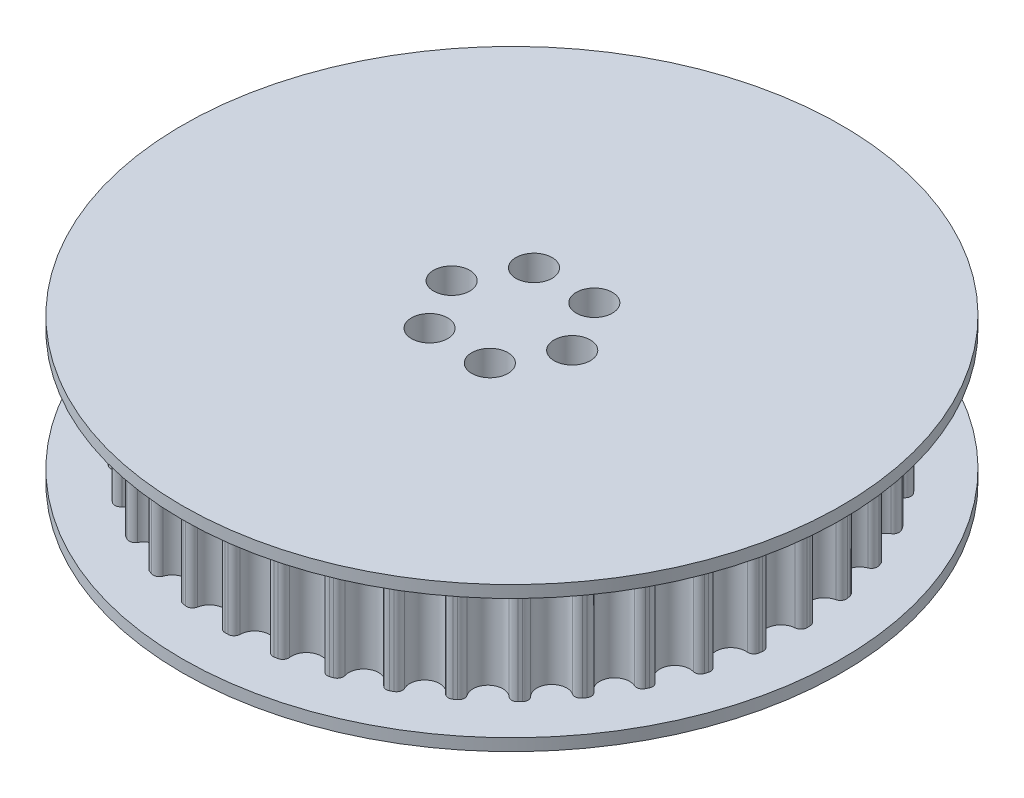
SolidWorks part; units mm, degrees
material "PETG"
ref_plane "Front Plane" through (0, 0, 0) normal (0, 0, 1) x (1, 0, 0)
ref_plane "Top Plane" through (0, 0, 0) normal (0, 1, 0) x (1, 0, 0)
ref_plane "Right Plane" through (0, 0, 0) normal (1, 0, 0) x (0, 0, -1)
sketch "Sketch5" plane through (0, 0, 0) normal (0, 1, 0) x (1, 0, 0)
  line L0 (0, 9.7022) -> (0, 50009.7022) construction
  line L1 (0, 0) -> (0, 46.5575) construction
  line L3 (0, 0) -> (-3.9957, 49.4953) construction
  line L5 (0, 0) -> (3.9957, 49.4953) construction
  circle A0 centre (0, 0) radius 49.6563 construction
  circle A2 centre (0, 0) radius 47.3449 construction
  arc A3 (-2.4772, 46.3129) -> (2.4772, 46.3129) centre (0, 46.5575) ccw
  arc A43 (3.8097, 47.1914) -> (3.5472, 47.2119) centre (0, 0) ccw
  arc A45 (-3.5472, 47.2119) -> (-3.8097, 47.1914) centre (0, 0) ccw
  arc A46 (-2.4772, 46.3129) -> (-3.5472, 47.2119) centre (-3.4723, 46.2147) ccw
  arc A47 (3.5472, 47.2119) -> (2.4772, 46.3129) centre (3.4723, 46.2147) ccw
  arc A48 (4.984, 46.1106) -> (9.8742, 45.3158) centre (7.4684, 45.9546) ccw
  arc A49 (4.984, 46.1106) -> (4.072, 47.1695) centre (3.986, 46.1732) ccw
  arc A50 (4.072, 47.1695) -> (3.8097, 47.1914) centre (0, 0) ccw
  arc A51 (11.0746, 46.0315) -> (9.8742, 45.3158) centre (10.8407, 45.0592) ccw
  arc A52 (11.3304, 45.9692) -> (11.0746, 46.0315) centre (0, 0) ccw
  arc A53 (12.3162, 44.714) -> (17.0155, 43.1451) centre (14.7433, 44.1615) ccw
  arc A54 (12.3162, 44.714) -> (11.5858, 45.9055) centre (11.3411, 44.9359) ccw
  arc A55 (11.5858, 45.9055) -> (11.3304, 45.9692) centre (0, 0) ccw
  arc A56 (18.3152, 43.6589) -> (17.0155, 43.1451) centre (17.9283, 42.7367) ccw
  arc A57 (18.5576, 43.5564) -> (18.3152, 43.6589) centre (0, 0) ccw
  arc A58 (19.3293, 42.1593) -> (23.7161, 39.8569) centre (21.6364, 41.2247) ccw
  arc A59 (19.3293, 42.1593) -> (18.7995, 43.4525) centre (18.4025, 42.5347) ccw
  arc A60 (18.7995, 43.4525) -> (18.5576, 43.5564) centre (0, 0) ccw
  arc A61 (25.0814, 40.1556) -> (23.7161, 39.8569) centre (24.5516, 39.3074) ccw
  arc A62 (25.3043, 40.0155) -> (25.0814, 40.1556) centre (0, 0) ccw
  arc A63 (25.8418, 38.5127) -> (29.8025, 35.5364) centre (27.9691, 37.2201) ccw
  arc A64 (25.8418, 38.5127) -> (25.5264, 39.8742) centre (24.9872, 39.032) ccw
  arc A65 (25.5264, 39.8742) -> (25.3043, 40.0155) centre (0, 0) ccw
  arc A66 (31.198, 35.6122) -> (29.8025, 35.5364) centre (30.539, 34.86) ccw
  arc A67 (31.3955, 35.4382) -> (31.198, 35.6122) centre (0, 0) ccw
  arc A68 (31.685, 33.8686) -> (35.117, 30.2956) centre (33.5774, 32.2515) ccw
  arc A69 (31.685, 33.8686) -> (31.5921, 35.2631) centre (30.9248, 34.5183) ccw
  arc A70 (31.5921, 35.2631) -> (31.3955, 35.4382) centre (0, 0) ccw
  arc A71 (36.5066, 30.1465) -> (35.117, 30.2956) centre (35.7355, 29.5098) ccw
  arc A72 (36.6736, 29.9431) -> (36.5066, 30.1465) centre (0, 0) ccw
  arc A73 (36.7076, 28.3474) -> (39.522, 24.2701) centre (38.3161, 26.4477) ccw
  arc A74 (36.7076, 28.3474) -> (36.8395, 29.7387) centre (36.0614, 29.1106) ccw
  arc A75 (36.8395, 29.7387) -> (36.6736, 29.9431) centre (0, 0) ccw
  arc A76 (40.8697, 23.9001) -> (39.522, 24.2701) centre (40.0064, 23.3953) ccw
  arc A77 (41.0019, 23.6725) -> (40.8697, 23.9001) centre (0, 0) ccw
  arc A78 (40.7795, 22.092) -> (42.9034, 17.616) centre (42.0624, 19.9589) ccw
  arc A79 (40.7795, 22.092) -> (41.1329, 23.4441) centre (40.2641, 22.949) ccw
  arc A80 (41.1329, 23.4441) -> (41.0019, 23.6725) centre (0, 0) ccw
  arc A81 (44.1743, 17.0346) -> (42.9034, 17.616) centre (43.2412, 16.6748) ccw
  arc A82 (44.2683, 16.7887) -> (44.1743, 17.0346) centre (0, 0) ccw
  arc A83 (43.7952, 15.2644) -> (45.1736, 10.5057) centre (44.7194, 12.9531) ccw
  arc A84 (43.7952, 15.2644) -> (44.361, 16.5424) centre (43.424, 16.193) ccw
  arc A85 (44.361, 16.5424) -> (44.2683, 16.7887) centre (0, 0) ccw
  arc A86 (46.3348, 9.728) -> (45.1736, 10.5057) centre (45.3561, 9.5225) ccw
  arc A87 (46.3881, 9.4702) -> (46.3348, 9.728) centre (0, 0) ccw
  arc A88 (45.6767, 8.0415) -> (46.2739, 3.1233) centre (46.2181, 5.6119) ccw
  arc A89 (45.6767, 8.0415) -> (46.4401, 9.2121) centre (45.4592, 9.0176) ccw
  arc A90 (46.4401, 9.2121) -> (46.3881, 9.4702) centre (0, 0) ccw
  arc A91 (47.2952, 2.1694) -> (46.2739, 3.1233) centre (46.2963, 2.1236) ccw
  arc A92 (47.3065, 1.9064) -> (47.2952, 2.1694) centre (0, 0) ccw
  arc A93 (46.3751, 0.6103) -> (46.1756, -4.34) centre (46.5198, -1.8747) ccw
  arc A94 (46.3751, 0.6103) -> (47.3164, 1.6433) centre (46.317, 1.6086) ccw
  arc A95 (47.3164, 1.6433) -> (47.3065, 1.9064) centre (0, 0) ccw
  arc A96 (47.0307, -5.4454) -> (46.1756, -4.34) centre (46.0374, -5.3304) ccw
  arc A97 (46.9997, -5.7068) -> (47.0307, -5.4454) centre (0, 0) ccw
  arc A98 (45.8725, -6.8367) -> (44.8815, -11.6909) centre (45.6166, -9.3127) ccw
  arc A99 (45.8725, -6.8367) -> (46.9673, -5.968) centre (45.9753, -5.842) ccw
  arc A100 (46.9673, -5.968) -> (46.9997, -5.7068) centre (0, 0) ccw
  arc A101 (45.5482, -12.9191) -> (44.8815, -11.6909) centre (44.5862, -12.6463) ccw
  arc A102 (45.4757, -13.1722) -> (45.5482, -12.9191) centre (0, 0) ccw
  arc A103 (44.1818, -14.1066) -> (42.4249, -18.739) centre (43.5321, -16.5095) ccw
  arc A104 (44.1818, -14.1066) -> (45.4017, -13.4248) centre (44.4428, -13.1413) ccw
  arc A105 (45.4017, -13.4248) -> (45.4757, -13.1722) centre (0, 0) ccw
  arc A106 (42.886, -20.0583) -> (42.4249, -18.739) centre (41.9802, -19.6346) ccw
  arc A107 (42.7738, -20.2964) -> (42.886, -20.0583) centre (0, 0) ccw
  arc A108 (41.3468, -21.0112) -> (38.8696, -25.3017) centre (40.32, -23.2788) ccw
  arc A109 (41.3468, -21.0112) -> (42.6603, -20.5339) centre (41.7592, -20.1002) ccw
  arc A110 (42.6603, -20.5339) -> (42.7738, -20.2964) centre (0, 0) ccw
  arc A111 (39.1131, -26.6779) -> (38.8696, -25.3017) centre (38.2869, -26.1145) ccw
  arc A112 (38.9641, -26.895) -> (39.1131, -26.6779) centre (0, 0) ccw
  arc A113 (37.4409, -27.3716) -> (34.3076, -31.2092) centre (36.0637, -29.4451) ccw
  arc A114 (37.4409, -27.3716) -> (38.814, -27.1112) centre (37.9942, -26.5386) ccw
  arc A115 (38.814, -27.1112) -> (38.9641, -26.895) centre (0, 0) ccw
  arc A116 (34.3271, -32.6066) -> (34.3076, -31.2092) centre (33.6021, -31.9179) ccw
  arc A117 (34.1453, -32.797) -> (34.3271, -32.6066) centre (0, 0) ccw
  arc A118 (32.5653, -33.0231) -> (28.857, -36.3084) centre (30.8734, -34.8488) ccw
  arc A119 (32.5653, -33.0231) -> (33.9624, -32.9863) centre (33.2451, -32.2896) ccw
  arc A120 (33.9624, -32.9863) -> (34.1453, -32.797) centre (0, 0) ccw
  arc A121 (28.6521, -37.6908) -> (28.857, -36.3084) centre (28.0469, -36.8948) ccw
  arc A122 (28.4421, -37.8496) -> (28.6521, -37.6908) centre (0, 0) ccw
  arc A123 (26.8464, -37.8193) -> (22.659, -40.4672) centre (24.8834, -39.35) ccw
  arc A124 (26.8464, -37.8193) -> (28.2312, -38.0071) centre (27.6349, -37.2044) ccw
  arc A125 (28.2312, -38.0071) -> (28.4421, -37.8496) centre (0, 0) ccw
  arc A126 (22.235, -41.7989) -> (22.659, -40.4672) centre (21.7654, -40.916) ccw
  arc A127 (22.0023, -41.9219) -> (22.235, -41.7989) centre (0, 0) ccw
  arc A128 (20.4321, -41.636) -> (15.8742, -43.5779) centre (18.249, -42.832) ccw
  arc A129 (20.4321, -41.636) -> (21.7689, -42.0436) centre (21.3091, -41.1555) ccw
  arc A130 (21.7689, -42.0436) -> (22.0023, -41.9219) centre (0, 0) ccw
  arc A131 (15.2421, -44.8243) -> (15.8742, -43.5779) centre (14.9202, -43.8776) ccw
  arc A132 (14.9926, -44.9084) -> (15.2421, -44.8243) centre (0, 0) ccw
  arc A133 (13.4886, -44.3744) -> (8.6782, -45.56) centre (11.1419, -45.2047) ccw
  arc A134 (13.4886, -44.3744) -> (14.7427, -44.9911) centre (14.4313, -44.0408) ccw
  arc A135 (14.7427, -44.9911) -> (14.9926, -44.9084) centre (0, 0) ccw
  arc A136 (7.8544, -46.6889) -> (8.6782, -45.56) centre (7.6885, -45.7027) ccw
  arc A137 (7.5947, -46.7318) -> (7.8544, -46.6889) centre (0, 0) ccw
  arc A138 (6.1958, -45.9634) -> (1.2575, -46.3621) centre (3.7463, -46.4066) ccw
  arc A139 (6.1958, -45.9634) -> (7.3347, -46.7733) centre (7.1798, -45.7854) ccw
  arc A140 (7.3347, -46.7733) -> (7.5947, -46.7318) centre (0, 0) ccw
  arc A141 (0.2632, -47.3442) -> (1.2575, -46.3621) centre (0.2577, -46.3442) ccw
  arc A142 (0, -47.3449) -> (0.2632, -47.3442) centre (0, 0) ccw
  arc A143 (-1.2575, -46.3621) -> (-6.1958, -45.9634) centre (-3.7463, -46.4066) ccw
  arc A144 (-1.2575, -46.3621) -> (-0.2632, -47.3442) centre (-0.2577, -46.3442) ccw
  arc A145 (-0.2632, -47.3442) -> (0, -47.3449) centre (0, 0) ccw
  arc A146 (-7.3347, -46.7733) -> (-6.1958, -45.9634) centre (-7.1798, -45.7854) ccw
  arc A147 (-7.5947, -46.7318) -> (-7.3347, -46.7733) centre (0, 0) ccw
  arc A148 (-8.6782, -45.56) -> (-13.4886, -44.3744) centre (-11.1419, -45.2047) ccw
  arc A149 (-8.6782, -45.56) -> (-7.8544, -46.6889) centre (-7.6885, -45.7027) ccw
  arc A150 (-7.8544, -46.6889) -> (-7.5947, -46.7318) centre (0, 0) ccw
  arc A151 (-14.7427, -44.9911) -> (-13.4886, -44.3744) centre (-14.4313, -44.0408) ccw
  arc A152 (-14.9926, -44.9084) -> (-14.7427, -44.9911) centre (0, 0) ccw
  arc A153 (-15.8742, -43.5779) -> (-20.4321, -41.636) centre (-18.249, -42.832) ccw
  arc A154 (-15.8742, -43.5779) -> (-15.2421, -44.8243) centre (-14.9202, -43.8776) ccw
  arc A155 (-15.2421, -44.8243) -> (-14.9926, -44.9084) centre (0, 0) ccw
  arc A156 (-21.7689, -42.0436) -> (-20.4321, -41.636) centre (-21.3091, -41.1555) ccw
  arc A157 (-22.0023, -41.9219) -> (-21.7689, -42.0436) centre (0, 0) ccw
  arc A158 (-22.659, -40.4672) -> (-26.8464, -37.8193) centre (-24.8834, -39.35) ccw
  arc A159 (-22.659, -40.4672) -> (-22.235, -41.7989) centre (-21.7654, -40.916) ccw
  arc A160 (-22.235, -41.7989) -> (-22.0023, -41.9219) centre (0, 0) ccw
  arc A161 (-28.2312, -38.0071) -> (-26.8464, -37.8193) centre (-27.6349, -37.2044) ccw
  arc A162 (-28.4421, -37.8496) -> (-28.2312, -38.0071) centre (0, 0) ccw
  arc A163 (-28.857, -36.3084) -> (-32.5653, -33.0231) centre (-30.8734, -34.8488) ccw
  arc A164 (-28.857, -36.3084) -> (-28.6521, -37.6908) centre (-28.0469, -36.8948) ccw
  arc A165 (-28.6521, -37.6908) -> (-28.4421, -37.8496) centre (0, 0) ccw
  arc A166 (-33.9624, -32.9863) -> (-32.5653, -33.0231) centre (-33.2451, -32.2896) ccw
  arc A167 (-34.1453, -32.797) -> (-33.9624, -32.9863) centre (0, 0) ccw
  arc A168 (-34.3076, -31.2092) -> (-37.4409, -27.3716) centre (-36.0637, -29.4451) ccw
  arc A169 (-34.3076, -31.2092) -> (-34.3271, -32.6066) centre (-33.6021, -31.9179) ccw
  arc A170 (-34.3271, -32.6066) -> (-34.1453, -32.797) centre (0, 0) ccw
  arc A171 (-38.814, -27.1112) -> (-37.4409, -27.3716) centre (-37.9942, -26.5386) ccw
  arc A172 (-38.9641, -26.895) -> (-38.814, -27.1112) centre (0, 0) ccw
  arc A173 (-38.8696, -25.3017) -> (-41.3468, -21.0112) centre (-40.32, -23.2788) ccw
  arc A174 (-38.8696, -25.3017) -> (-39.1131, -26.6779) centre (-38.2869, -26.1145) ccw
  arc A175 (-39.1131, -26.6779) -> (-38.9641, -26.895) centre (0, 0) ccw
  arc A176 (-42.6603, -20.5339) -> (-41.3468, -21.0112) centre (-41.7592, -20.1002) ccw
  arc A177 (-42.7738, -20.2964) -> (-42.6603, -20.5339) centre (0, 0) ccw
  arc A178 (-42.4249, -18.739) -> (-44.1818, -14.1066) centre (-43.5321, -16.5095) ccw
  arc A179 (-42.4249, -18.739) -> (-42.886, -20.0583) centre (-41.9802, -19.6346) ccw
  arc A180 (-42.886, -20.0583) -> (-42.7738, -20.2964) centre (0, 0) ccw
  arc A181 (-45.4017, -13.4248) -> (-44.1818, -14.1066) centre (-44.4428, -13.1413) ccw
  arc A182 (-45.4757, -13.1722) -> (-45.4017, -13.4248) centre (0, 0) ccw
  arc A183 (-44.8815, -11.6909) -> (-45.8725, -6.8367) centre (-45.6166, -9.3127) ccw
  arc A184 (-44.8815, -11.6909) -> (-45.5482, -12.9191) centre (-44.5862, -12.6463) ccw
  arc A185 (-45.5482, -12.9191) -> (-45.4757, -13.1722) centre (0, 0) ccw
  arc A186 (-46.9673, -5.968) -> (-45.8725, -6.8367) centre (-45.9753, -5.842) ccw
  arc A187 (-46.9997, -5.7068) -> (-46.9673, -5.968) centre (0, 0) ccw
  arc A188 (-46.1756, -4.34) -> (-46.3751, 0.6103) centre (-46.5198, -1.8747) ccw
  arc A189 (-46.1756, -4.34) -> (-47.0307, -5.4454) centre (-46.0374, -5.3304) ccw
  arc A190 (-47.0307, -5.4454) -> (-46.9997, -5.7068) centre (0, 0) ccw
  arc A191 (-47.3164, 1.6433) -> (-46.3751, 0.6103) centre (-46.317, 1.6086) ccw
  arc A192 (-47.3065, 1.9064) -> (-47.3164, 1.6433) centre (0, 0) ccw
  arc A193 (-46.2739, 3.1233) -> (-45.6767, 8.0415) centre (-46.2181, 5.6119) ccw
  arc A194 (-46.2739, 3.1233) -> (-47.2952, 2.1694) centre (-46.2963, 2.1236) ccw
  arc A195 (-47.2952, 2.1694) -> (-47.3065, 1.9064) centre (0, 0) ccw
  arc A196 (-46.4401, 9.2121) -> (-45.6767, 8.0415) centre (-45.4592, 9.0176) ccw
  arc A197 (-46.3881, 9.4702) -> (-46.4401, 9.2121) centre (0, 0) ccw
  arc A198 (-45.1736, 10.5057) -> (-43.7952, 15.2644) centre (-44.7194, 12.9531) ccw
  arc A199 (-45.1736, 10.5057) -> (-46.3348, 9.728) centre (-45.3561, 9.5225) ccw
  arc A200 (-46.3348, 9.728) -> (-46.3881, 9.4702) centre (0, 0) ccw
  arc A201 (-44.361, 16.5424) -> (-43.7952, 15.2644) centre (-43.424, 16.193) ccw
  arc A202 (-44.2683, 16.7887) -> (-44.361, 16.5424) centre (0, 0) ccw
  arc A203 (-42.9034, 17.616) -> (-40.7795, 22.092) centre (-42.0624, 19.9589) ccw
  arc A204 (-42.9034, 17.616) -> (-44.1743, 17.0346) centre (-43.2412, 16.6748) ccw
  arc A205 (-44.1743, 17.0346) -> (-44.2683, 16.7887) centre (0, 0) ccw
  arc A206 (-41.1329, 23.4441) -> (-40.7795, 22.092) centre (-40.2641, 22.949) ccw
  arc A207 (-41.0019, 23.6725) -> (-41.1329, 23.4441) centre (0, 0) ccw
  arc A208 (-39.522, 24.2701) -> (-36.7076, 28.3474) centre (-38.3161, 26.4477) ccw
  arc A209 (-39.522, 24.2701) -> (-40.8697, 23.9001) centre (-40.0064, 23.3953) ccw
  arc A210 (-40.8697, 23.9001) -> (-41.0019, 23.6725) centre (0, 0) ccw
  arc A211 (-36.8395, 29.7387) -> (-36.7076, 28.3474) centre (-36.0614, 29.1106) ccw
  arc A212 (-36.6736, 29.9431) -> (-36.8395, 29.7387) centre (0, 0) ccw
  arc A213 (-35.117, 30.2956) -> (-31.685, 33.8686) centre (-33.5774, 32.2515) ccw
  arc A214 (-35.117, 30.2956) -> (-36.5066, 30.1465) centre (-35.7355, 29.5098) ccw
  arc A215 (-36.5066, 30.1465) -> (-36.6736, 29.9431) centre (0, 0) ccw
  arc A216 (-31.5921, 35.2631) -> (-31.685, 33.8686) centre (-30.9248, 34.5183) ccw
  arc A217 (-31.3955, 35.4382) -> (-31.5921, 35.2631) centre (0, 0) ccw
  arc A218 (-29.8025, 35.5364) -> (-25.8418, 38.5127) centre (-27.9691, 37.2201) ccw
  arc A219 (-29.8025, 35.5364) -> (-31.198, 35.6122) centre (-30.539, 34.86) ccw
  arc A220 (-31.198, 35.6122) -> (-31.3955, 35.4382) centre (0, 0) ccw
  arc A221 (-25.5264, 39.8742) -> (-25.8418, 38.5127) centre (-24.9872, 39.032) ccw
  arc A222 (-25.3043, 40.0155) -> (-25.5264, 39.8742) centre (0, 0) ccw
  arc A223 (-23.7161, 39.8569) -> (-19.3293, 42.1593) centre (-21.6364, 41.2247) ccw
  arc A224 (-23.7161, 39.8569) -> (-25.0814, 40.1556) centre (-24.5516, 39.3074) ccw
  arc A225 (-25.0814, 40.1556) -> (-25.3043, 40.0155) centre (0, 0) ccw
  arc A226 (-18.7995, 43.4525) -> (-19.3293, 42.1593) centre (-18.4025, 42.5347) ccw
  arc A227 (-18.5576, 43.5564) -> (-18.7995, 43.4525) centre (0, 0) ccw
  arc A228 (-17.0155, 43.1451) -> (-12.3162, 44.714) centre (-14.7433, 44.1615) ccw
  arc A229 (-17.0155, 43.1451) -> (-18.3152, 43.6589) centre (-17.9283, 42.7367) ccw
  arc A230 (-18.3152, 43.6589) -> (-18.5576, 43.5564) centre (0, 0) ccw
  arc A231 (-11.5858, 45.9055) -> (-12.3162, 44.714) centre (-11.3411, 44.9359) ccw
  arc A232 (-11.3304, 45.9692) -> (-11.5858, 45.9055) centre (0, 0) ccw
  arc A233 (-9.8742, 45.3158) -> (-4.984, 46.1106) centre (-7.4684, 45.9546) ccw
  arc A234 (-9.8742, 45.3158) -> (-11.0746, 46.0315) centre (-10.8407, 45.0592) ccw
  arc A235 (-11.0746, 46.0315) -> (-11.3304, 45.9692) centre (0, 0) ccw
  arc A236 (-4.072, 47.1695) -> (-4.984, 46.1106) centre (-3.986, 46.1732) ccw
  arc A237 (-3.8097, 47.1914) -> (-4.072, 47.1695) centre (0, 0) ccw
  point P9 (0, 44.0683)
  point P14 (0, 49.6563)
  point P17 (0, 0)
  point P28 (-3.7463, 47.185)
  point P31 (0, 47.3449)
  dimension "D3" = 2.4892
  dimension "D4" = 99.3127
  dimension "D6" = 1
  dimension "D2" = 5.588
  dimension "D1" = 3.2766
  dimension "D5" = 8
  dimension "D7" = 39
extrude "Boss-Extrude3" add sketch "Sketch5" along normal mid plane 20 contours A2 | A45 A237 A236 A233 A234 A235 A232 A231 A228 A229 A230 A227 A226 A223 A224 A225 A222 A221 A218 A219 A220 A217 A216 A213 A214 A215 A212 A211 A208 A209 A210 A207 A206 A203 A204 A205 A202 A201 A198 A199 A200 A197 A196 region at (0, 0, 0)
sketch "Sketch2" plane through (0, 10, 0) normal (0, 1, 0) x (1, 0, 0)
  circle A0 centre (0, 0) radius 54.6563
  dimension "D1" = 109.3127
extrude "Boss-Extrude2" add sketch "Sketch2" along normal blind 2
mirror "Mirror1" about plane through (0, 0, 0) normal (0, 1, 0) of "Boss-Extrude2"
sketch "Sketch3" plane through (0, 12, 0) normal (0, 1, 0) x (1, 0, 0)
  line L0 (0, 0) -> (10, 0) construction
  circle A0 centre (10, 0) radius 1.7
  circle A1 centre (5, -8.6603) radius 1.7
  circle A2 centre (-5, -8.6603) radius 1.7
  circle A3 centre (-10, 0) radius 1.7
  circle A4 centre (-5, 8.6603) radius 1.7
  circle A5 centre (5, 8.6603) radius 1.7
  dimension "D1" = 10
  dimension "D2" = 3.4
  dimension "D3" = 6
extrude "Cut-Extrude1" cut sketch "Sketch3" against normal through all
sketch "Sketch4" plane through (0, 12, 0) normal (0, 1, 0) x (1, 0, 0)
  line L0 (0, 0) -> (5, -8.6603) construction
  circle A0 centre (5, -8.6603) radius 3
  circle A1 centre (-5, -8.6603) radius 3
  circle A2 centre (-10, 0) radius 3
  circle A3 centre (-5, 8.6603) radius 3
  circle A4 centre (5, 8.6603) radius 3
  circle A5 centre (10, 0) radius 3
  dimension "D1" = 6
  dimension "D2" = 6
extrude "Cut-Extrude2" cut sketch "Sketch4" against normal offset from surface (14 mm away) 10 up to face at (10, -12, 1.7)
equation "\"pitch\"= 8mm"
equation "\"n\"= 39"
equation "\"pitch_dia\"= \"pitch\" * \"n\" / PI"
equation "\"belt_width\"= 20mm"
equation "\"D1@Sketch2\"=\"pitch_dia\"+10.00mm"
equation "\"D4@Sketch5\"=\"pitch_dia\""
equation "\"D1@Boss-Extrude3\"=\"belt_width\""
equation "\"D7@Sketch5\"=\"n\""
equation "\"D5@Sketch5\"=\"pitch\""
